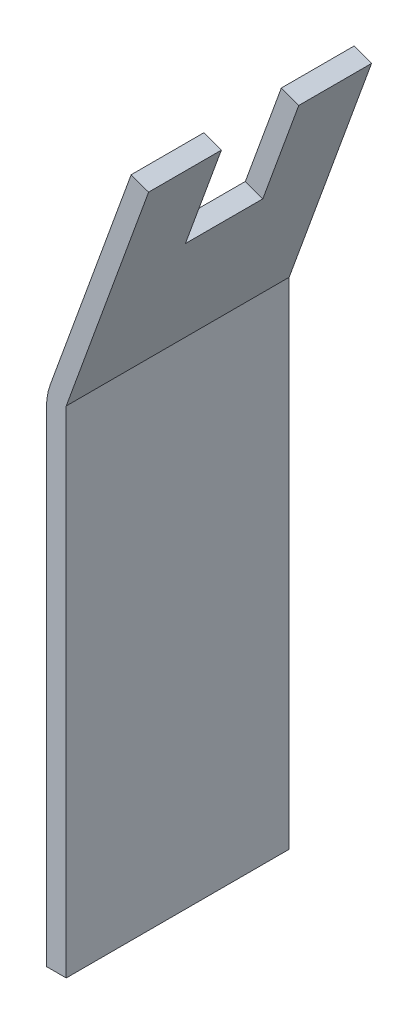
SolidWorks part; units mm, degrees
ref_plane "Plan de face" through (0, 0, 0) normal (0, 0, 1) x (1, 0, 0)
ref_plane "Plan de dessus" through (0, 0, 0) normal (0, 1, 0) x (1, 0, 0)
ref_plane "Plan de droite" through (0, 0, 0) normal (1, 0, 0) x (0, 0, -1)
sketch "Esquisse1" plane through (0, 0, 0) normal (0, 0, 1) x (1, 0, 0)
  line L0 (0, 0) -> (0, 80)
  line L1 (0, 80) -> (13.6808, 117.5877)
  line L2 (13.6808, 117.5877) -> (16.4999, 116.5616)
  line L3 (16.4999, 116.5616) -> (3.1925, 80)
  line L4 (3.1925, 80) -> (3.1925, 0)
  line L5 (3.1925, 0) -> (0, 0)
  line L6 (0, 80) -> (50000, 80) construction
  dimension "D1" = 80
  dimension "D2" = 40
  dimension "D3" = 3
  dimension "D4" = 70
extrude "Boss.-Extru.1" add sketch "Esquisse1" along normal blind 18 and the other way blind 18
fillet "Congé1" radius 10 1 edges at (0, 80, 0)
sketch "Esquisse2" plane through (-25.7115, 9.3582, 0) normal (-0.9397, 0.342, 0) x (0, 0, 1)
  line L0 (-6.25, 115.1754) -> (-6.25, 98.1754)
  line L1 (-18, 115.1754) -> (18, 115.1754) construction
  line L2 (-6.25, 98.1754) -> (6.25, 98.1754)
  line L3 (6.25, 98.1754) -> (6.25, 115.1754)
  line L4 (0, 115.1754) -> (0, 50115.1754) construction
  line L5 (-6.25, 115.1754) -> (6.25, 115.1754)
  point P8 (0, 115.1754)
  dimension "D1" = 17
  dimension "D2" = 12.5
extrude "Enlèv. mat.-Extru.1" cut sketch "Esquisse2" against normal up to surface (3 mm away) up to face at (9.8462, 98.2808, 0)
